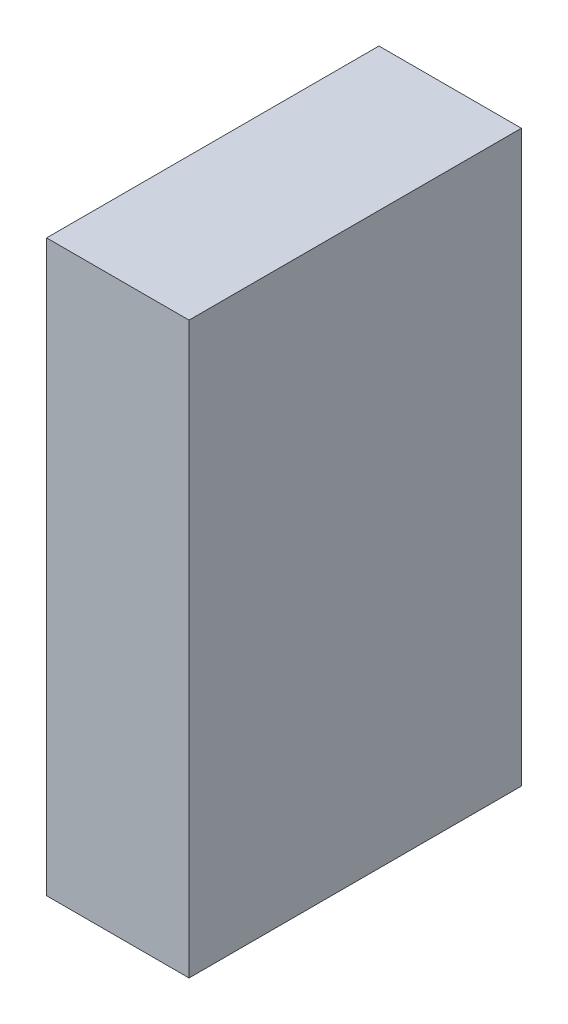
SolidWorks part; units mm, degrees
material "Pine"
ref_plane "Front Plane" through (0, 0, 0) normal (0, 0, 1) x (1, 0, 0)
ref_plane "Top Plane" through (0, 0, 0) normal (0, 1, 0) x (1, 0, 0)
ref_plane "Right Plane" through (0, 0, 0) normal (1, 0, 0) x (0, 0, -1)
sketch "Sketch1" plane through (0, 0, 0) normal (0, 1, 0) x (1, 0, 0)
  line L1 (19.05, -44.45) -> (-19.05, -44.45)
  line L2 (19.05, -44.45) -> (19.05, 44.45)
  line L3 (19.05, 44.45) -> (-19.05, 44.45)
  line L4 (-19.05, -44.45) -> (-19.05, 44.45)
  line L5 (19.05, -44.45) -> (-19.05, 44.45) construction
  line L6 (19.05, 44.45) -> (-19.05, -44.45) construction
  point P0 (0, 0)
  dimension "D1" = 38.1
  dimension "D2" = 88.9
extrude "Boss-Extrude1" add sketch "Sketch1" along normal up to surface (152.4 mm away)
